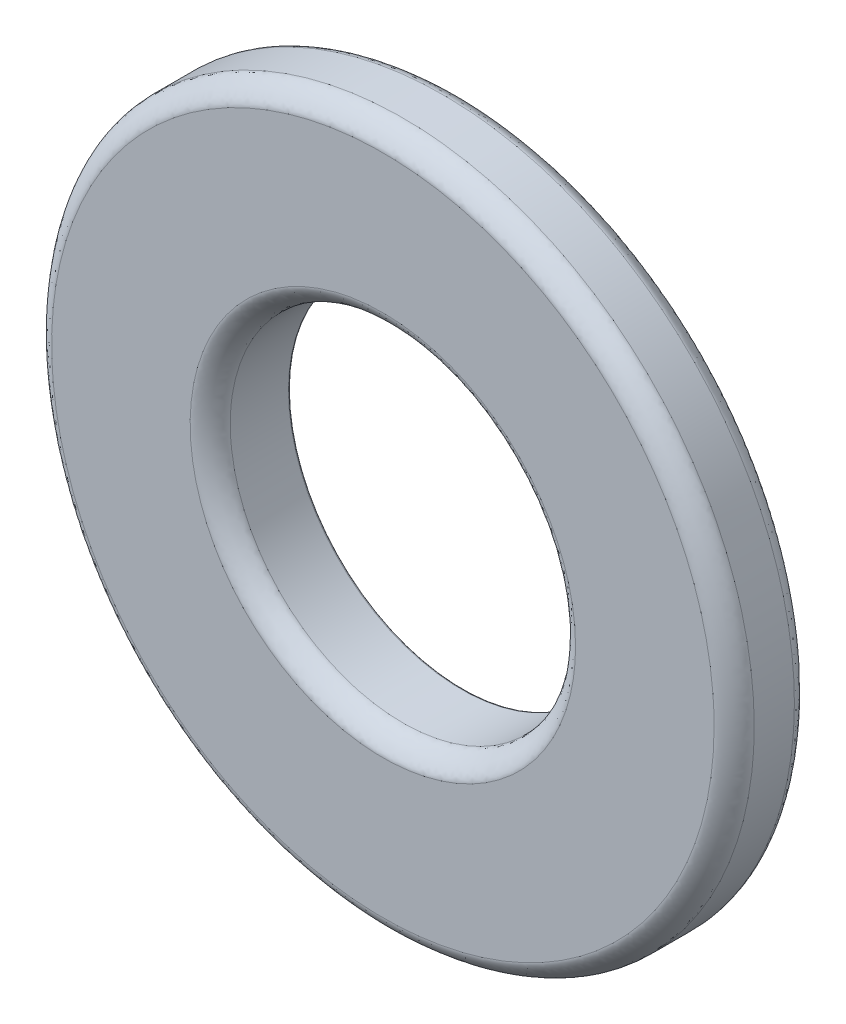
SolidWorks part; units mm, degrees
ref_plane "Alzado" through (0, 0, 0) normal (1, 0, 0) x (0, 1, 0)
ref_plane "Planta" through (0, 0, 0) normal (0, 0, 1) x (0, 1, 0)
ref_plane "Vista lateral" through (0, 0, 0) normal (0, 1, 0) x (-1, 0, 0)
sketch "Croquis2" plane through (0, 0, 0) normal (0, 0, 1) x (0, 1, 0)
  circle A0 centre (0, 0) radius 8.6
  circle A1 centre (0, 0) radius 17.5
  dimension "D1" = 17.2
  dimension "D2" = 35
extrude "Saliente-Extruir1" add sketch "Croquis2" along normal blind 4
fillet "Redondeo1" radius 1 3 edges at (17.5, 0, 0) (8.6, 0, 4) (17.5, 0, 4) conic radius 2
fillet "Redondeo2" radius 0.1 1 edges at (8.6, 0, 0)
